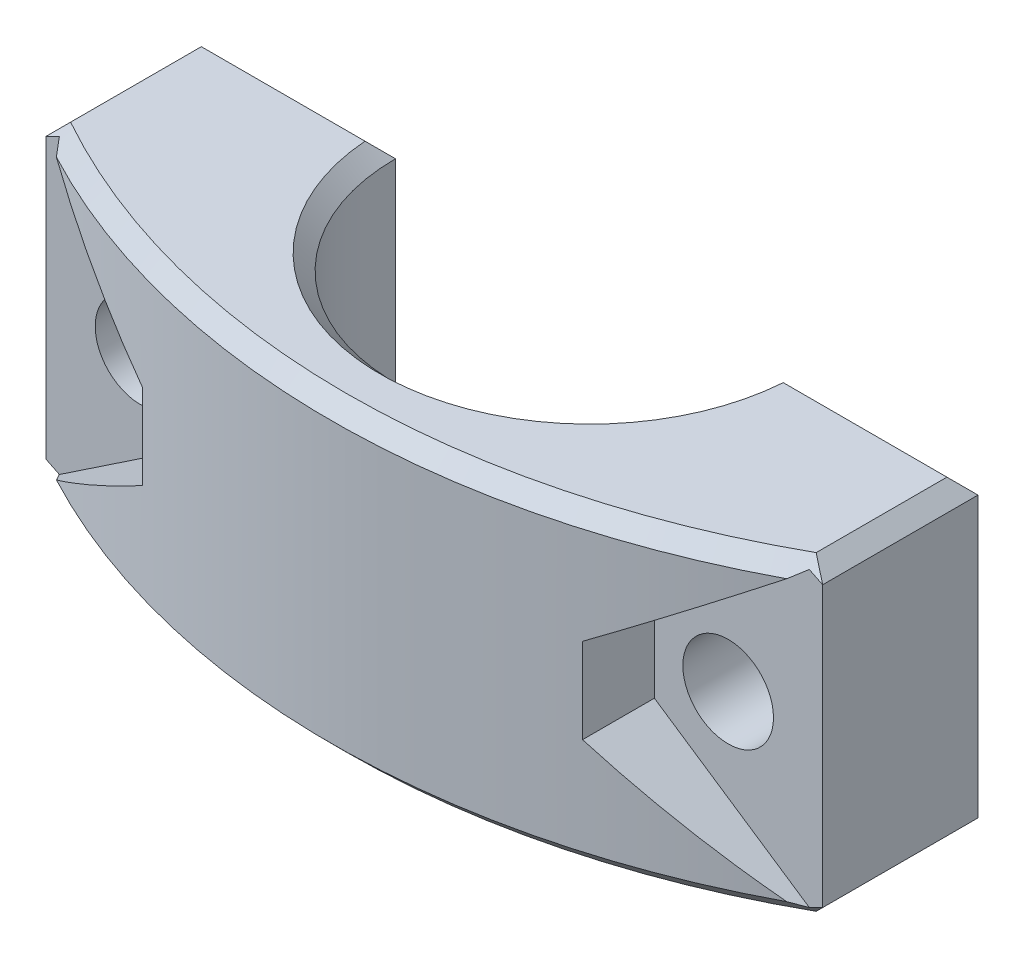
SolidWorks part; units mm, degrees
material "ABS"
ref_plane "Plano frontal" through (0, 0, 0) normal (0, 0, 1) x (1, 0, 0)
ref_plane "Plano superior" through (0, 0, 0) normal (0, 1, 0) x (1, 0, 0)
ref_plane "Plano direito" through (0, 0, 0) normal (1, 0, 0) x (0, 0, -1)
sketch "Esboço1" plane through (0, 0, 0) normal (0, 0, 1) x (1, 0, 0)
  line L1 (-15, 6) -> (15, 6)
  line L2 (-15, 6) -> (-15, -6)
  line L3 (-15, -6) -> (15, -6)
  line L4 (15, 6) -> (15, -6)
  line L5 (-15, 6) -> (15, -6) construction
  line L6 (-15, -6) -> (15, 6) construction
  point P0 (0, 0)
  dimension "D1" = 30
  dimension "D2" = 12
extrude "Ressalto-extrusão1" add sketch "Esboço1" along normal mid plane 10
sketch "Esboço2" plane through (0, 6, 0) normal (0, 1, 0) x (1, 0, 0)
  line L0 (15, 5) -> (-15, 5) construction
  arc A0 (-7.5, 5) -> (7.5, 5) centre (0, 5) ccw
  dimension "D1" = 7.5
extrude "Corte-extrusão1" cut sketch "Esboço2" against normal through all and the other way through all
sketch "Esboço3" plane through (0, 0, 5) normal (0, 0, 1) x (1, 0, 0)
  line L0 (-15, 0) -> (15, 0) construction
  line L1 (-15, 6) -> (-15, -6) construction
  line L2 (15, -6) -> (15, 6) construction
  circle A0 centre (11.35, 0) radius 1.75
  point P8 (0, 0)
  dimension "D1" = 3.5
  dimension "D2" = 11.35
extrude "Corte-extrusão2" cut sketch "Esboço3" against normal through all
mirror "Espelhar1" about plane through (0, 0, 0) normal (1, 0, 0) of "Corte-extrusão2"
sketch "Esboço4" plane through (0, 0, 5) normal (0, 0, 1) x (1, 0, 0)
  line L0 (-8.5, 1.6454) -> (-15, 6)
  line L1 (-8.5, 1.6454) -> (-11.35, 3.2909)
  line L2 (-11.35, 3.2909) -> (-14.2, 1.6454)
  line L3 (-14.2, 1.6454) -> (-14.2, -1.6454)
  line L4 (-14.2, -1.6454) -> (-11.35, -3.2909)
  line L5 (-11.35, -3.2909) -> (-8.5, -1.6454)
  line L6 (-8.5, -1.6454) -> (-8.5, 1.6454)
  line L7 (-15, 6) -> (-15, -6)
  line L8 (-15, -6) -> (-8.5, -1.6454)
  circle A0 centre (-11.35, 0) radius 2.85 construction
  circle M3 centre (-11.35, 0) radius 1.75
  line M7 (-15, 6) -> (-15, -6)
  dimension "D1" = 5.7
extrude "Corte-extrusão3" cut sketch "Esboço4" against normal blind 4 contours L8 L5 L4 L3 L2 L1 L0 M7 | L5 L6 L1 L2 L3 L4 M3 region at (-9.9182, 2.48, 5) region at (-8.5871, 0, 5)
mirror "Espelhar2" about plane through (0, 0, 0) normal (1, 0, 0) of "Corte-extrusão3"
sketch "Esboço5" plane through (0, -6, 0) normal (0, -1, 0) x (1, 0, 0)
  line L0 (-15, 5) -> (15, 5) construction
  arc A0 (-15, 1) -> (15, 1) centre (0, -25.125) cw
  point P3 (0, 5)
extrude "Corte-extrusão4" cut sketch "Esboço5" against normal through all and the other way through all
chamfer "Chanfro2" distance 0.6 angle 45 12 edges at (-15, 6, -2) (-11.25, 6, -5) (0, 6, 2.5) (11.25, 6, -5) (15, 6, -2) (0, 6, 5) (11.25, -6, -5) (0, -6, 2.5) (-11.25, -6, -5) (-15, -6, -2) (0, -6, 5) (15, -6, -2)
